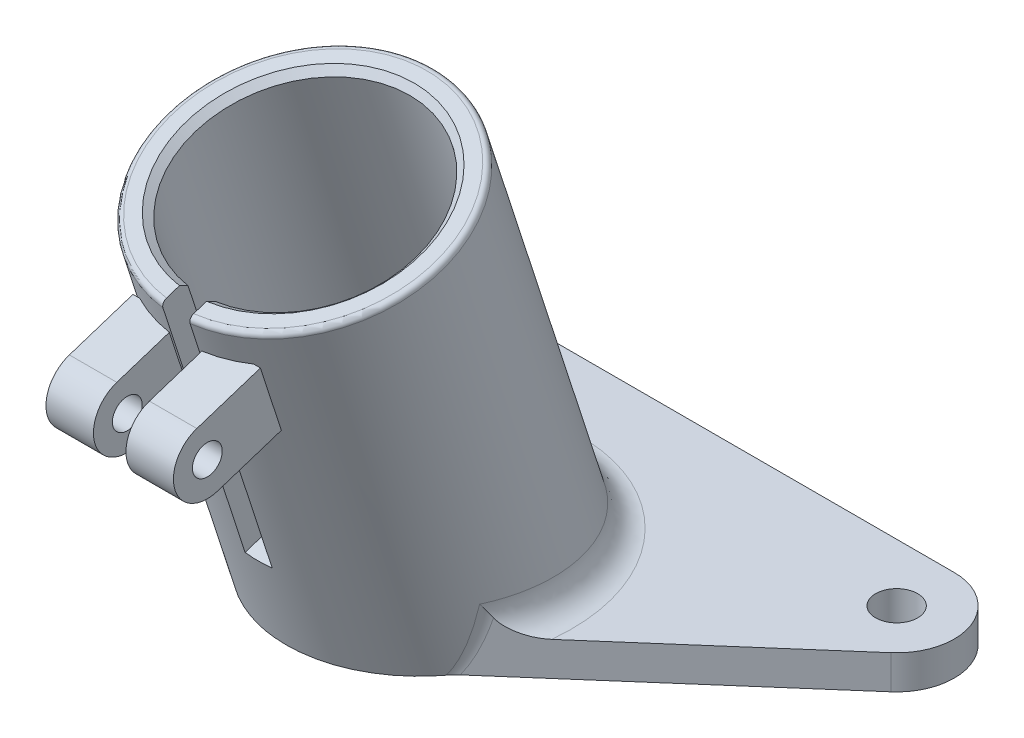
SolidWorks part; units mm, degrees
material "ABS"
ref_plane "Front Plane" through (0, 0, 0) normal (0, 0, 1) x (1, 0, 0)
ref_plane "Top Plane" through (0, 0, 0) normal (0, 1, 0) x (1, 0, 0)
ref_plane "Right Plane" through (0, 0, 0) normal (1, 0, 0) x (0, 0, -1)
sketch "Sketch1" plane through (0, 0, 0) normal (0, 1, 0) x (1, 0, 0)
  line L0 (-22.5, 12) -> (22.5, 12) construction
  line L5 (-22.5, 16.25) -> (22.5, 16.25)
  line L6 (-25.2941, 8.7976) -> (-6.5743, -7.5352)
  line L7 (25.2941, 8.7976) -> (6.5743, -7.5352)
  arc A0 (-6.5743, -7.5352) -> (6.5743, -7.5352) centre (0, 0) ccw
  circle A2 centre (-22.5, 12) radius 1.55
  circle A3 centre (22.5, 12) radius 1.55
  circle A4 centre (-22.5, 12) radius 4.25
  circle A5 centre (22.5, 12) radius 4.25
  point P0 (0, 0)
  point P13 (0, 12)
  dimension "D2" = 20
  dimension "D3" = 3.1
  dimension "D6" = 8.5
  dimension "D4" = 45
  dimension "D5" = 12
extrude "Boss-Extrude1" add sketch "Sketch1" along normal blind 2.5 contours L0 A4 L6 A0 L7 A5 | A2 A4 | A4 L0 A5 L5 | A5 A3 | A0 region at (-20.7908, 0, -8.2405) region at (0, 0, -14.181) region at (0, 0, -3.2808) region at (19.5798, 0, -14.9202)
sketch3d "3DSketch1"
  line L0 (0, 0, 0) -> (0, 28.2698, 0) construction
  line L1 (0, 0, 0) -> (0, 28.5317, 9.2705)
  dimension "D1" = 18
  dimension "D2" = 30
sweep "Sweep1" add path "3DSketch1" circular profile diameter 20 parameters "D3"=20
sketch "Sketch20" plane through (0, 28.5317, 9.2705) normal (0, 0.9511, 0.309) x (1, 0, 0)
  circle A0 centre (0, 0) radius 8.1
  dimension "D1" = 16.2
extrude "Cut-Extrude1" cut sketch "Sketch20" against normal blind 20 and the other way through all
sketch "Sketch21" plane through (0, 0, 0) normal (0, -0.9511, -0.309) x (1, 0, 0)
  circle A6 centre (0, 0) radius 10
  arc A7 (10, 0) -> (-10, 0) centre (0, 0) ccw construction
sketch "Sketch22" plane through (0, 0, -16.25) normal (0, 0, -1) x (-1, 0, 0)
  line L1 (-22.5, 0) -> (22.5, 0)
  line L2 (-22.5, 0) -> (-22.5, -12.6031)
  line L3 (-22.5, -12.6031) -> (22.5, -12.6031)
  line L4 (22.5, 0) -> (22.5, -12.6031)
  line L5 (-22.5, 0) -> (22.5, -12.6031) construction
  line L6 (-22.5, -12.6031) -> (22.5, 0) construction
  point P4 (0, -6.3016)
extrude "Boss-Extrude5" add sketch "Sketch21" along normal blind 5
extrude "Cut-Extrude3" cut sketch "Sketch22" against normal through all both and the other way through all
ref_plane "Plane1" through (0, 0, 0) normal (0, -0.309, 0.9511) x (1, 0, 0)
sketch "Sketch28" plane through (0, 0, 0) normal (0, -0.309, 0.9511) x (1, 0, 0)
  line L0 (10, 30) -> (-10, 30) construction
  line L1 (-1, 30) -> (1, 30)
  line L2 (-1, 30) -> (-1, 10)
  line L3 (-1, 10) -> (1, 10)
  line L4 (1, 30) -> (1, 10)
  line L5 (-1, 30) -> (1, 10) construction
  line L6 (-1, 10) -> (1, 30) construction
  line L7 (0, 0) -> (0, 30) construction
  point P4 (0, 20)
  dimension "D1" = 20
  dimension "D2" = 2
extrude "Cut-Extrude4" cut sketch "Sketch28" against normal blind 5 and the other way through all
ref_plane "Plane2" through (0, 0, 0) normal (1, 0, 0) x (0, 0, -1)
sketch "Sketch29" plane through (0, 0, 0) normal (1, 0, 0) x (0, 0, -1)
  line L0 (-21.0402, 19.4502) -> (-7.7254, 23.7764) construction
  line L1 (0, 0) -> (-9.2705, 28.5317) construction
  line L2 (-17.1256, 23.3508) -> (-21.8128, 21.8278)
  line L3 (-20.2677, 17.0725) -> (-15.5805, 18.5955)
  line L4 (-15.5805, 18.5955) -> (-17.1256, 23.3508)
  line L5 (0.2401, 31.6219) -> (-18.7334, 25.457) construction
  circle A0 centre (-21.0402, 19.4502) radius 1.1
  circle A1 centre (-21.0402, 19.4502) radius 2.5
  dimension "D1" = 2.2
  dimension "D2" = 5
  dimension "D3" = 5
  dimension "D4" = 14
extrude "Boss-Extrude6" add sketch "Sketch29" along normal blind 3.5 from offset 1.2 contours A0 A1 | A1 L0 L4 L2 | L0 A1 L3 L4 region at (0, 19.8302, 18.6408) region at (0, 21.8066, 18.2378) region at (0, 19.191, 17.3879)
extrude "Boss-Extrude7" add sketch "Sketch29<3>" against normal blind 3.5 from offset 1.2 contours A1 L0 L4 L2 | L0 A1 L3 L4 | A0 A1 region at (0, 19.8302, 18.6408) region at (0, 21.8066, 18.2378) region at (0, 19.191, 17.3879) offset against normal yes
sketch "Sketch29<3>" plane through (0, 0, 0) normal (1, 0, 0) x (0, 0, -1) same geometry as "Sketch29"
chamfer "Chamfer1" distance 0.5 angle 45 1 edges at (0, 31.0347, 1.567)
fillet "Fillet1" radius 2 3 edges at (-8.543, 1.0839, 5.8175) (8.543, 1.0839, 5.8175) (0, 2.5, -9.7023)
fillet "Fillet3" radius 0.4 1 edges at (0, 31.6219, -0.2401)
